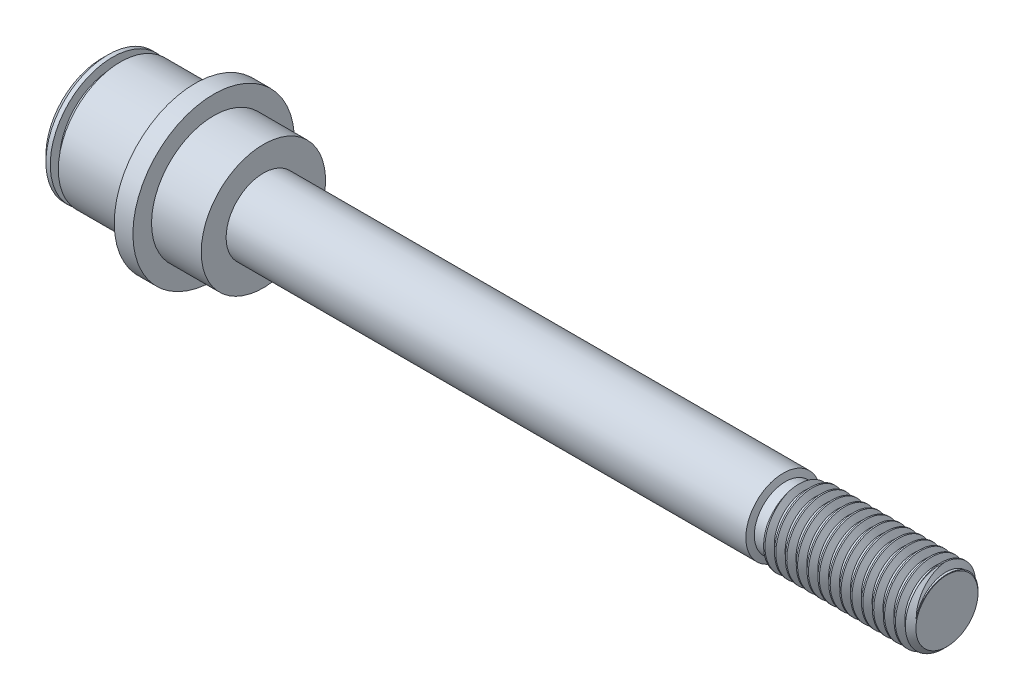
SolidWorks part; units mm, degrees
ref_plane "Front Plane" through (0, 0, 0) normal (0, 0, 1) x (1, 0, 0)
ref_plane "Top Plane" through (0, 0, 0) normal (0, 1, 0) x (1, 0, 0)
ref_plane "Right Plane" through (0, 0, 0) normal (1, 0, 0) x (0, 0, -1)
sketch "Sketch2" plane through (0, 0, 0) normal (0, 0, 1) x (1, 0, 0)
  line L0 (0, 0) -> (136, 0)
  line L1 (136, 0) -> (136, 6)
  line L2 (136, 6) -> (26, 6)
  line L3 (26, 6) -> (26, 10)
  line L4 (26, 10) -> (18, 10)
  line L5 (18, 10) -> (18, 13)
  line L6 (18, 13) -> (15, 13)
  line L7 (15, 13) -> (15, 10)
  line L8 (15, 10) -> (0, 10)
  line L9 (0, 10) -> (0, 0)
  point P3 (16.5, 13)
  point P14 (17.1967, -7.3622)
  point P15 (29.4725, -16.4181)
  dimension "D1" = 110
  dimension "D2" = 8
  dimension "D3" = 3
  dimension "D4" = 15
  dimension "D5" = 10
  dimension "D6" = 6
  dimension "D7" = 13
revolve "Revolve3" add sketch "Sketch2" angle 360 about L0
chamfer "Chamfer1" distance 1 angle 45 2 edges at (136, 0, 6) (0, 0, 10)
thread "Thread1" pitch 1.75 method cut profile "Thread Profile3" start angle 0, offset 1, length 25, pitch 1.75, diameter 12
ref_plane "Plane3" through (137, 0, 6) normal (0, -1, 0) x (0, 0, 1)
sketch "Thread Profile3" plane through (137, 0, 6) normal (0, -1, 0) x (0, 0, 1)
  line L0 (0, 0) -> (0, 1.75) construction
  line L11 (0, 0) -> (0, 1.5312)
  line L12 (0, 1.5312) -> (-0.9472, 0.9844)
  line L13 (-0.9472, 0.9844) -> (-0.9472, 0.5469)
  line L15 (-0.9472, 0.5469) -> (0, 0)
  line L17 (-0.9472, 0.7656) -> (0, 0.7656) construction
  point P2 (0, 0)
  dimension "Pitch" = 1.75
  dimension "Profile_Angle" = 60
  dimension "Profile_Land" = 0.4375
  dimension "Profile_Height" = 0.9472
sketch "Sketch16" plane through (0, 0, 0) normal (0, 0, 1) x (1, 0, 0)
  line L0 (15, 13) -> (15, -13) construction
  line L1 (1.7, 11.5) -> (3, 11.5)
  line L2 (1.7, 11.5) -> (1.7, 8.5)
  line L3 (1.7, 8.5) -> (3, 8.5)
  line L4 (3, 11.5) -> (3, 8.5)
  line L5 (0, 0) -> (20, 0) construction
  line L6 (0, 9) -> (0, -9) construction
  dimension "D1" = 1.3
  dimension "D2" = 3
  dimension "D3" = 12
  dimension "D4" = 8.5
revolve "Cut-Revolve1" cut sketch "Sketch16" angle 360 about L5
sketch "Sketch17" plane through (0, 0, 0) normal (0, 0, 1) x (1, 0, 0)
  line L0 (111, 6.5) -> (111, 5) construction
  line L1 (109.454, 6.5) -> (112.546, 6.5)
  line L2 (109.454, 6.5) -> (110, 5)
  line L3 (110, 5) -> (112, 5)
  line L4 (112.546, 6.5) -> (112, 5)
  line L5 (0, 0) -> (146.1468, 0) construction
  line L6 (136, -5) -> (136, 5) construction
  point P9 (106.3896, 8.9844)
  point P10 (0, 0)
  point P11 (106.3896, 9.0286)
  point P12 (0, 0)
  point P13 (0, 0)
  point P14 (104.1506, 9.0144)
  dimension "D1" = 2
  dimension "D2" = 40
  dimension "D3" = 5
  dimension "D4" = 6.5
  dimension "D5" = 24
revolve "Cut-Revolve2" cut sketch "Sketch17" angle 360 about L5
